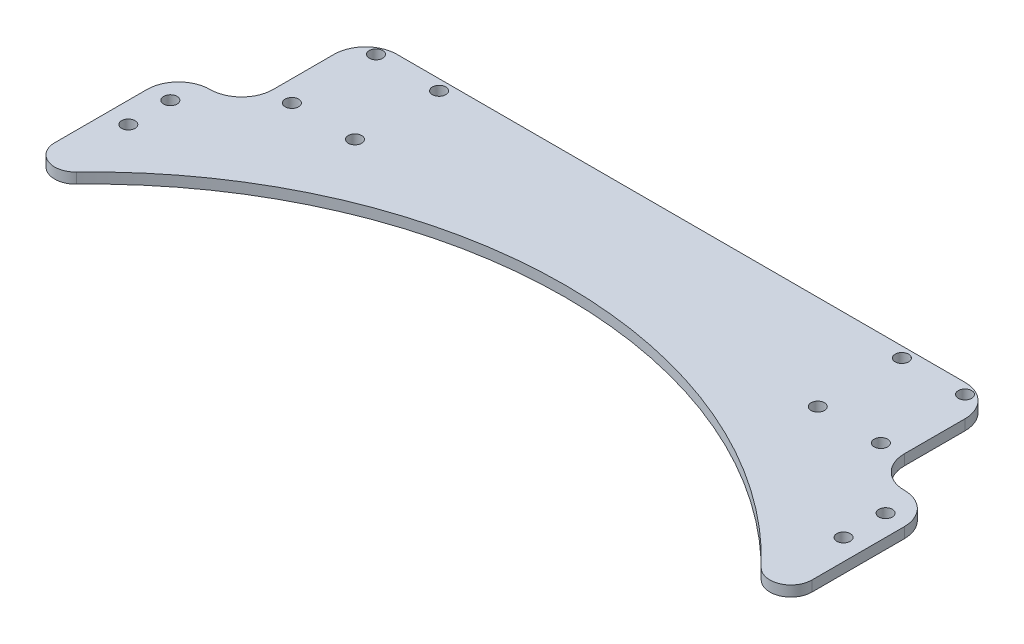
SolidWorks part; units mm, degrees
ref_plane "Front Plane" through (0, 0, 0) normal (0, 0, 1) x (1, 0, 0)
ref_plane "Top Plane" through (0, 0, 0) normal (0, 1, 0) x (1, 0, 0)
ref_plane "Right Plane" through (0, 0, 0) normal (1, 0, 0) x (0, 0, -1)
sketch "Sketch1" plane through (0, 0, 0) normal (0, 1, 0) x (1, 0, 0)
  line L0 (0, 0) -> (0, 92.075)
  line L1 (0, 92.075) -> (228.6, 92.075)
  line L2 (228.6, 92.075) -> (228.6, 0)
  arc A0 (0, 0) -> (228.6, 0) centre (114.3, -85.725) cw
  dimension "D3" = 142.875
  dimension "D1" = 177.8
  dimension "D2" = 228.6
extrude "Boss-Extrude1" add sketch "Sketch1" along normal blind 3.175
sketch "Sketch3" plane through (0, 0, 0) normal (0, -1, 0) x (1, 0, 0)
  line L0 (228.6, -92.075) -> (0, -92.075) construction
  line L1 (114.3, -92.075) -> (114.3, -57.15) construction
  circle A2 centre (44.45, -63.5) radius 2.032 construction
  circle A3 centre (25.4, -63.5) radius 2.032 construction
  arc A8 (0, 0) -> (228.6, 0) centre (114.3, 85.725) ccw construction
  circle A17 centre (44.45, -88.9) radius 2.032 construction
  circle A18 centre (25.4, -88.9) radius 2.032 construction
  circle A19 centre (44.45, -63.5) radius 2.032
  circle A20 centre (25.4, -63.5) radius 2.032
  circle A21 centre (44.45, -88.9) radius 2.032
  circle A22 centre (25.4, -88.9) radius 2.032
  circle A23 centre (203.2, -63.5) radius 2.032
  circle A24 centre (203.2, -88.9) radius 2.032
  circle A25 centre (184.15, -88.9) radius 2.032
  circle A26 centre (184.15, -63.5) radius 2.032
  point P12 (114.3, -92.075)
extrude "Cut-Extrude1" cut sketch "Sketch3" against normal through all
fillet "Fillet1" radius 6.35 2 edges at (0, 1.5875, 0) (228.6, 1.5875, 0)
sketch "Sketch4" plane through (0, 0, 0) normal (0, -1, 0) x (1, 0, 0)
  line L0 (0, -54.6893) -> (19.05, -54.6893)
  line L1 (0, -92.075) -> (0, -17.3036) construction
  line L15 (19.05, -54.6893) -> (19.05, -92.075)
  line L16 (19.05, -92.075) -> (0, -92.075)
  line L17 (0, -92.075) -> (0, -54.6893)
  line L18 (19.05, -58.3161) -> (19.05, -40.393) construction
  line L19 (19.05, -58.3161) -> (19.05, -40.393) construction
  line L20 (209.55, -58.3161) -> (209.55, -40.393) construction
  line L21 (209.55, -58.3161) -> (209.55, -40.393) construction
  line L22 (228.6, -92.075) -> (228.6, -54.6893)
  line L23 (228.6, -17.3036) -> (228.6, -92.075) construction
  line L24 (228.6, -54.6893) -> (209.55, -54.6893)
  line L25 (209.55, -54.6893) -> (209.55, -92.075)
  line L26 (228.6, -92.075) -> (0, -92.075) construction
  line L27 (209.55, -92.075) -> (228.6, -92.075)
  circle A0 centre (6.35, -33.1786) radius 2.032
  circle A1 centre (6.35, -45.8786) radius 2.032
  circle A3 centre (222.25, -33.1786) radius 2.032
  circle A4 centre (222.25, -45.8786) radius 2.032
  arc A6 (10.9436, -12.9194) -> (0, -17.3036) centre (6.35, -17.3036) ccw construction
  arc A7 (10.9436, -12.9194) -> (0, -17.3036) centre (6.35, -17.3036) ccw construction
  arc A8 (228.6, -17.3036) -> (217.6564, -12.9194) centre (222.25, -17.3036) ccw construction
  arc A9 (228.6, -17.3036) -> (217.6564, -12.9194) centre (222.25, -17.3036) ccw construction
  line M8 (0, -17.3036) -> (0, -92.075)
  line M9 (0, -92.075) -> (228.6, -92.075)
  line M10 (228.6, -92.075) -> (228.6, -17.3036)
  dimension "D2" = 4.064
  dimension "D1" = 12.7
  dimension "D3" = 15.875
extrude "Cut-Extrude2" cut sketch "Sketch4" against normal through all contours A0 | A1 | A3 | A4 | L15 L0 M8 M9 | L24 L25 M9 M10 region at (219.075, 0, -73.3822) region at (9.525, 0, -73.3822) region at (6.35, 0, -33.1786) region at (6.35, 0, -45.8786) region at (222.25, 0, -33.1786) region at (222.25, 0, -45.8786)
fillet "Fillet2" radius 9.525 6 edges at (209.55, 1.5875, -92.075) (209.55, 1.5875, -54.6893) (228.6, 1.5875, -54.6893) (19.05, 1.5875, -92.075) (19.05, 1.5875, -54.6893) (0, 1.5875, -54.6893)
